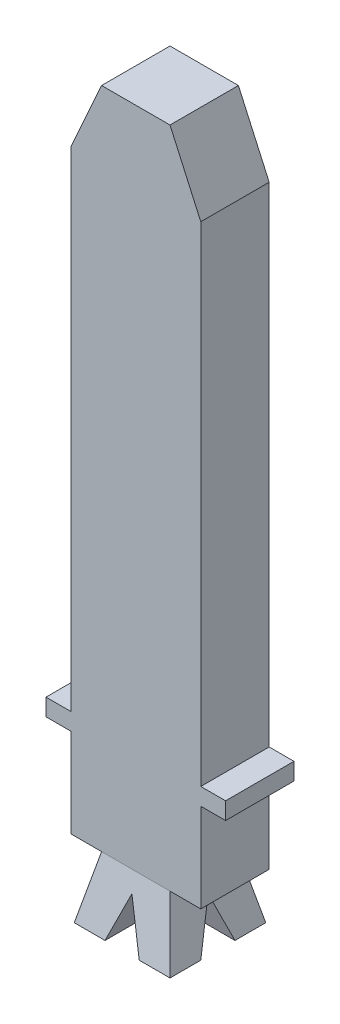
SolidWorks part; units mm, degrees
ref_plane "Front Plane" through (0, 0, 0) normal (0, 0, 1) x (1, 0, 0)
ref_plane "Top Plane" through (0, 0, 0) normal (0, 1, 0) x (1, 0, 0)
ref_plane "Right Plane" through (0, 0, 0) normal (1, 0, 0) x (0, 0, -1)
sketch "Sketch1" plane through (0, 0, 0) normal (0, 0, 1) x (1, 0, 0)
  line L0 (1.9, 0) -> (2.625, 0)
  line L2 (-1.9, 14.3) -> (-1.9, 0)
  line L4 (1.9, 14.3) -> (1.9, 0)
  line L5 (-2.625, 0) -> (-1.9, 0)
  line L6 (-2.625, 0) -> (-2.625, -0.5)
  line L7 (-2.625, -0.5) -> (-1.9, -0.5)
  line L8 (2.625, 0) -> (2.625, -0.5)
  line L9 (1.9, -0.5) -> (2.625, -0.5)
  line L11 (-1.9, -0.5) -> (-1.9, -3.1)
  line L12 (-1.9, -3.1) -> (1.9, -3.1)
  line L13 (1.9, -0.5) -> (1.9, -3.1)
  line L14 (-1, 16.3) -> (1, 16.3)
  line L15 (-1.9, 14.3) -> (-1, 16.3)
  line L16 (1, 16.3) -> (1.9, 14.3)
  point P9 (2.625, -0.25)
  dimension "D2" = 3.8
  dimension "D3" = 1.9
  dimension "D5" = 5.25
  dimension "D6" = 2.625
  dimension "D1" = 2.6
  dimension "D7" = 1.9
  dimension "D8" = 1.9
  dimension "D9" = 0.25
  dimension "D10" = 0.5
  dimension "D11" = 2
  dimension "D13" = 0.9
  dimension "D14" = 3.8
  dimension "D4" = 14.3
  dimension "D12" = 16.3
extrude "Boss-Extrude1" add sketch "Sketch1" along normal blind 2
ref_plane "Plane1" through (0, -4.9, 0) normal (0, -1, 0) x (-1, 0, 0)
sketch "Sketch2" plane through (0, -3.1, 0) normal (0, -1, 0) x (1, 0, 0)
  line L0 (-1.9, 2) -> (1.9, 2) construction
  line L1 (-1, 2) -> (1, 2)
  line L2 (-1, 2) -> (-1, 0)
  line L3 (-1, 0) -> (1, 0)
  line L4 (1, 2) -> (1, 0)
  line L5 (-1.9, 0) -> (1.9, 0) construction
  dimension "D1" = 2
  dimension "D2" = 2
  dimension "D3" = 1
sketch "Sketch3" plane through (0, -4.9, 0) normal (0, -1, 0) x (-1, 0, 0)
  line L1 (-1.4, 0.4) -> (1.4, 0.4)
  line L2 (-1.4, 0.4) -> (-1.4, -2.4)
  line L3 (-1.4, -2.4) -> (1.4, -2.4)
  line L4 (1.4, 0.4) -> (1.4, -2.4)
  dimension "D1" = 2.8
  dimension "D2" = 2.8
  dimension "D3" = 1.4
  dimension "D4" = 0.4
loft "Loft1" add profiles "Sketch2", "Sketch3" connector at (1, -3.1, 2) connector at (1.4, -4.9, 2.4)
ref_plane "Plane2" through (0, 0, 1.8) normal (0, 0, 1) x (1, 0, 0)
sketch "Sketch4" plane through (0, 0, 1.8) normal (0, 0, 1) x (1, 0, 0)
  line L0 (0, -3.6115) -> (-0.5, -4.9)
  line L1 (-1.1, -4.9) -> (1.1, -4.9) construction
  line L2 (-0.5, -4.9) -> (0.5, -4.9)
  line L3 (0.5, -4.9) -> (0, -3.6115)
  dimension "D1" = 0.5
  dimension "D2" = 0.5
  dimension "D3" = 3.6115
ref_plane "Plane3" through (1.8, 0, 0) normal (1, 0, 0) x (0, 0, -1)
sketch "Sketch5" plane through (1.8, 0, -1.8) normal (-1, 0, 0) x (0, 0, 1)
  line L0 (2.8, -3.6115) -> (2.3, -4.9)
  line L1 (1.4, -4.9) -> (4.2, -4.9) construction
  line L2 (2.3, -4.9) -> (3.3, -4.9)
  line L3 (3.3, -4.9) -> (2.8, -3.6115)
  line L4 (1.4, -4.9) -> (4.2, -4.9) construction
extrude "Cut-Extrude1" cut sketch "Sketch4" against normal through all both and the other way through all
extrude "Cut-Extrude2" cut sketch "Sketch5" against normal through all both and the other way through all
equation "\"D3@Sketch1\"=\"D2@Sketch1\"/2"
equation "\"D6@Sketch1\"=\"D5@Sketch1\"/2"
equation "\"D3@Sketch3\"=\"D1@Sketch3\"/2"
equation "\"D4@Sketch3\"=(\"D2@Sketch3\"-2)/2"
